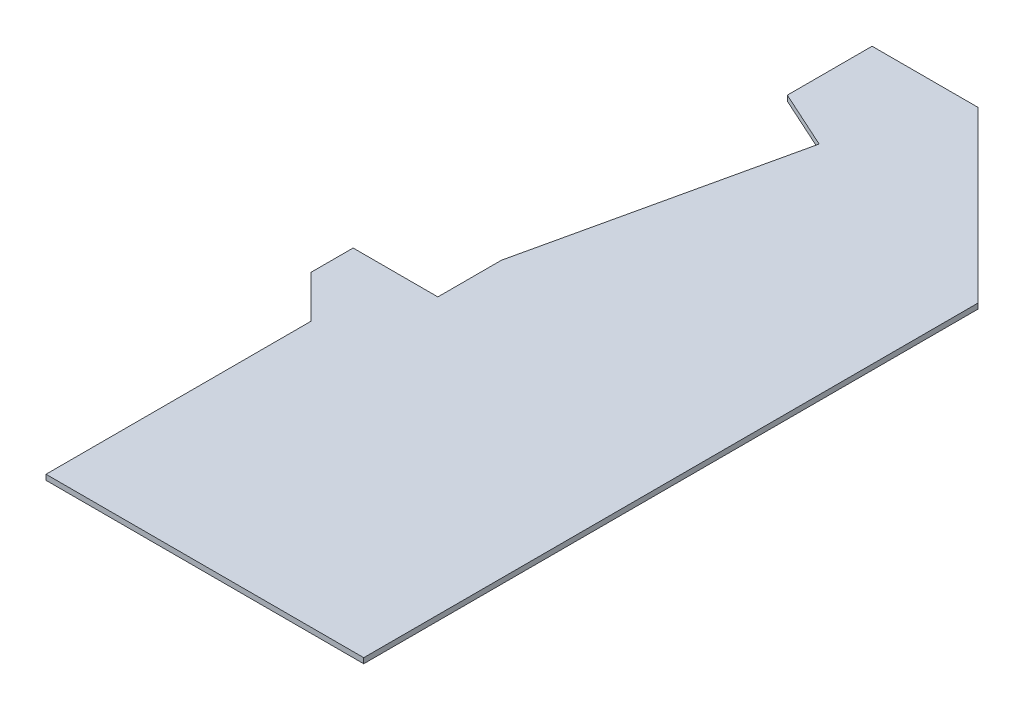
SolidWorks part; units mm, degrees
ref_plane "Front Plane" through (0, 0, 0) normal (0, 0, 1) x (1, 0, 0)
ref_plane "Top Plane" through (0, 0, 0) normal (0, 1, 0) x (1, 0, 0)
ref_plane "Right Plane" through (0, 0, 0) normal (1, 0, 0) x (0, 0, -1)
sketch "Sketch1" plane through (0, 0, 0) normal (0, 1, 0) x (1, 0, 0)
  line L0 (-108.5345, -3.9032) -> (-108.5345, 1469.2968)
  line L1 (-108.5345, -3.9032) -> (-870.5345, -3.9032)
  line L2 (-870.5345, -3.9032) -> (-870.5345, 631.0968)
  line L3 (-972.1345, 732.6968) -> (-972.1345, 834.2968)
  line L4 (-768.9345, 834.2968) -> (-768.9345, 986.6968)
  line L5 (-972.1345, 834.2968) -> (-768.9345, 834.2968)
  line L7 (-972.1345, 732.6968) -> (-870.5345, 631.0968)
  line L9 (-514.9345, 1875.6968) -> (-768.9345, 1875.6968)
  line L10 (-108.5345, 1469.2968) -> (-514.9345, 1875.6968)
  line L14 (-768.9345, 1672.4968) -> (-629.2345, 1608.9968)
  line L15 (-629.2345, 1608.9968) -> (-768.9345, 986.6968)
  line L16 (-768.9345, 1672.4968) -> (-768.9345, 1875.6968)
extrude "Boss-Extrude1" add sketch "Sketch1" along normal blind 12.7
